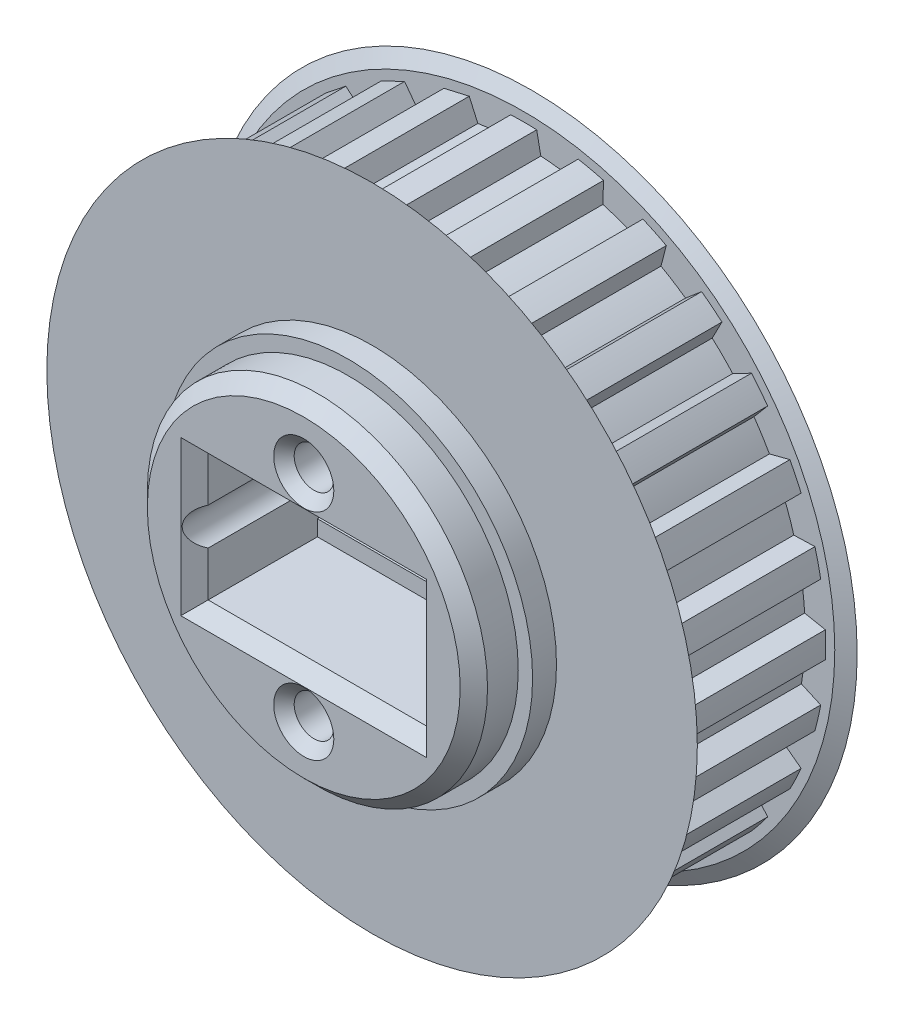
SolidWorks part; units mm, degrees
material "ABS"
ref_plane "Alzado" through (0, 0, 0) normal (0, 0, 1) x (1, 0, 0)
ref_plane "Planta" through (0, 0, 0) normal (0, 1, 0) x (1, 0, 0)
ref_plane "Vista lateral" through (0, 0, 0) normal (1, 0, 0) x (0, 0, -1)
sketch "Croquis1" plane through (0, 0, 0) normal (0, 0, 1) x (1, 0, 0)
  line L0 (0, 0) -> (0, 14.5885) construction
  line L1 (-0.95, 22.0796) -> (-1.25, 20.562)
  line L2 (0.95, 22.0796) -> (1.25, 20.562)
  line L3 (5.8393, 21.3146) -> (5.7941, 19.7684)
  line L4 (3.987, 21.7374) -> (3.3568, 20.3247)
  line L5 (10.4359, 19.4808) -> (10.0477, 17.9834)
  line L6 (8.724, 20.3052) -> (7.7953, 19.0681)
  line L7 (14.5091, 16.6702) -> (13.7975, 15.2967)
  line L8 (13.0236, 17.8548) -> (11.8429, 16.8554)
  line L9 (17.8548, 13.0236) -> (16.8554, 11.8429)
  line L10 (16.6702, 14.5091) -> (15.2967, 13.7975)
  line L11 (20.3052, 8.724) -> (19.0681, 7.7953)
  line L12 (19.4808, 10.4359) -> (17.9834, 10.0477)
  line L13 (21.7374, 3.987) -> (20.3247, 3.3568)
  line L14 (21.3146, 5.8393) -> (19.7684, 5.7941)
  line L15 (22.0796, -0.95) -> (20.562, -1.25)
  line L16 (22.0796, 0.95) -> (20.562, 1.25)
  line L17 (21.3146, -5.8393) -> (19.7684, -5.7941)
  line L18 (21.7374, -3.987) -> (20.3247, -3.3568)
  line L19 (19.4808, -10.4359) -> (17.9834, -10.0477)
  line L20 (20.3052, -8.724) -> (19.0681, -7.7953)
  line L21 (16.6702, -14.5091) -> (15.2967, -13.7975)
  line L22 (17.8548, -13.0236) -> (16.8554, -11.8429)
  line L23 (13.0236, -17.8548) -> (11.8429, -16.8554)
  line L24 (14.5091, -16.6702) -> (13.7975, -15.2967)
  line L25 (8.724, -20.3052) -> (7.7953, -19.0681)
  line L26 (10.4359, -19.4808) -> (10.0477, -17.9834)
  line L27 (3.987, -21.7374) -> (3.3568, -20.3247)
  line L28 (5.8393, -21.3146) -> (5.7941, -19.7684)
  line L29 (-0.95, -22.0796) -> (-1.25, -20.562)
  line L30 (0.95, -22.0796) -> (1.25, -20.562)
  line L31 (-5.8393, -21.3146) -> (-5.7941, -19.7684)
  line L32 (-3.987, -21.7374) -> (-3.3568, -20.3247)
  line L33 (-10.4359, -19.4808) -> (-10.0477, -17.9834)
  line L34 (-8.724, -20.3052) -> (-7.7953, -19.0681)
  line L35 (-14.5091, -16.6702) -> (-13.7975, -15.2967)
  line L36 (-13.0236, -17.8548) -> (-11.8429, -16.8554)
  line L37 (-17.8548, -13.0236) -> (-16.8554, -11.8429)
  line L38 (-16.6702, -14.5091) -> (-15.2967, -13.7975)
  line L39 (-20.3052, -8.724) -> (-19.0681, -7.7953)
  line L40 (-19.4808, -10.4359) -> (-17.9834, -10.0477)
  line L41 (-21.7374, -3.987) -> (-20.3247, -3.3568)
  line L42 (-21.3146, -5.8393) -> (-19.7684, -5.7941)
  line L43 (-22.0796, 0.95) -> (-20.562, 1.25)
  line L44 (-22.0796, -0.95) -> (-20.562, -1.25)
  line L45 (-21.3146, 5.8393) -> (-19.7684, 5.7941)
  line L46 (-21.7374, 3.987) -> (-20.3247, 3.3568)
  line L47 (-19.4808, 10.4359) -> (-17.9834, 10.0477)
  line L48 (-20.3052, 8.724) -> (-19.0681, 7.7953)
  line L49 (-16.6702, 14.5091) -> (-15.2967, 13.7975)
  line L50 (-17.8548, 13.0236) -> (-16.8554, 11.8429)
  line L51 (-13.0236, 17.8548) -> (-11.8429, 16.8554)
  line L52 (-14.5091, 16.6702) -> (-13.7975, 15.2967)
  line L53 (-14.5091, 16.6702) -> (-13.0236, 17.8548)
  line L54 (-8.724, 20.3052) -> (-7.7953, 19.0681)
  line L55 (-10.4359, 19.4808) -> (-10.0477, 17.9834)
  line L56 (-10.4359, 19.4808) -> (-8.724, 20.3052)
  line L57 (-3.987, 21.7374) -> (-3.3568, 20.3247)
  line L58 (-5.8393, 21.3146) -> (-5.7941, 19.7684)
  line L59 (-5.8393, 21.3146) -> (-3.987, 21.7374)
  arc A0 (-13.7975, 15.2967) -> (-15.2967, 13.7975) centre (0, 0) ccw
  arc A1 (3.3568, 20.3247) -> (1.25, 20.562) centre (0, 0) ccw
  arc A2 (-10.0477, 17.9834) -> (-11.8429, 16.8554) centre (0, 0) ccw
  arc A3 (-5.7941, 19.7684) -> (-7.7953, 19.0681) centre (0, 0) ccw
  arc A9 (-16.6702, 14.5091) -> (-17.8548, 13.0236) centre (0, 0) ccw
  arc A10 (-19.4808, 10.4359) -> (-20.3052, 8.724) centre (0, 0) ccw
  arc A11 (5.8393, 21.3146) -> (3.987, 21.7374) centre (0, 0) ccw
  arc A12 (0.95, 22.0796) -> (-0.95, 22.0796) centre (0, 0) ccw
  arc A16 (10.4359, 19.4808) -> (8.724, 20.3052) centre (0, 0) ccw
  arc A17 (14.5091, 16.6702) -> (13.0236, 17.8548) centre (0, 0) ccw
  arc A18 (17.8548, 13.0236) -> (16.6702, 14.5091) centre (0, 0) ccw
  arc A19 (20.3052, 8.724) -> (19.4808, 10.4359) centre (0, 0) ccw
  arc A20 (21.7374, 3.987) -> (21.3146, 5.8393) centre (0, 0) ccw
  arc A21 (22.0796, -0.95) -> (22.0796, 0.95) centre (0, 0) ccw
  arc A22 (21.3146, -5.8393) -> (21.7374, -3.987) centre (0, 0) ccw
  arc A23 (19.4808, -10.4359) -> (20.3052, -8.724) centre (0, 0) ccw
  arc A24 (16.6702, -14.5091) -> (17.8548, -13.0236) centre (0, 0) ccw
  arc A25 (13.0236, -17.8548) -> (14.5091, -16.6702) centre (0, 0) ccw
  arc A26 (-5.8393, -21.3146) -> (-3.987, -21.7374) centre (0, 0) ccw
  arc A27 (-10.4359, -19.4808) -> (-8.724, -20.3052) centre (0, 0) ccw
  arc A28 (-14.5091, -16.6702) -> (-13.0236, -17.8548) centre (0, 0) ccw
  arc A29 (-20.3052, -8.724) -> (-19.4808, -10.4359) centre (0, 0) ccw
  arc A30 (-21.7374, -3.987) -> (-21.3146, -5.8393) centre (0, 0) ccw
  arc A31 (-22.0796, 0.95) -> (-22.0796, -0.95) centre (0, 0) ccw
  arc A32 (-21.3146, 5.8393) -> (-21.7374, 3.987) centre (0, 0) ccw
  arc A33 (-0.95, -22.0796) -> (0.95, -22.0796) centre (0, 0) ccw
  arc A34 (3.987, -21.7374) -> (5.8393, -21.3146) centre (0, 0) ccw
  arc A35 (8.724, -20.3052) -> (10.4359, -19.4808) centre (0, 0) ccw
  arc A36 (7.7953, 19.0681) -> (5.7941, 19.7684) centre (0, 0) ccw
  arc A37 (11.8429, 16.8554) -> (10.0477, 17.9834) centre (0, 0) ccw
  arc A39 (-1.25, 20.562) -> (-3.3568, 20.3247) centre (0, 0) ccw
  arc A43 (15.2967, 13.7975) -> (13.7975, 15.2967) centre (0, 0) ccw
  arc A44 (17.9834, 10.0477) -> (16.8554, 11.8429) centre (0, 0) ccw
  arc A45 (19.7684, 5.7941) -> (19.0681, 7.7953) centre (0, 0) ccw
  arc A46 (20.562, 1.25) -> (20.3247, 3.3568) centre (0, 0) ccw
  arc A47 (20.3247, -3.3568) -> (20.562, -1.25) centre (0, 0) ccw
  arc A48 (19.0681, -7.7953) -> (19.7684, -5.7941) centre (0, 0) ccw
  arc A49 (16.8554, -11.8429) -> (17.9834, -10.0477) centre (0, 0) ccw
  arc A50 (13.7975, -15.2967) -> (15.2967, -13.7975) centre (0, 0) ccw
  arc A51 (10.0477, -17.9834) -> (11.8429, -16.8554) centre (0, 0) ccw
  arc A52 (5.7941, -19.7684) -> (7.7953, -19.0681) centre (0, 0) ccw
  arc A53 (1.25, -20.562) -> (3.3568, -20.3247) centre (0, 0) ccw
  arc A54 (-3.3568, -20.3247) -> (-1.25, -20.562) centre (0, 0) ccw
  arc A55 (-7.7953, -19.0681) -> (-5.7941, -19.7684) centre (0, 0) ccw
  arc A56 (-11.8429, -16.8554) -> (-10.0477, -17.9834) centre (0, 0) ccw
  arc A57 (-15.2967, -13.7975) -> (-13.7975, -15.2967) centre (0, 0) ccw
  arc A58 (-17.9834, -10.0477) -> (-16.8554, -11.8429) centre (0, 0) ccw
  arc A59 (-19.7684, -5.7941) -> (-19.0681, -7.7953) centre (0, 0) ccw
  arc A60 (-20.562, -1.25) -> (-20.3247, -3.3568) centre (0, 0) ccw
  arc A61 (-20.3247, 3.3568) -> (-20.562, 1.25) centre (0, 0) ccw
  arc A62 (-19.0681, 7.7953) -> (-19.7684, 5.7941) centre (0, 0) ccw
  arc A63 (-16.8554, 11.8429) -> (-17.9834, 10.0477) centre (0, 0) ccw
  arc A71 (-17.8548, -13.0236) -> (-16.6702, -14.5091) centre (0, 0) ccw
  circle A72 centre (0, 0) radius 1.5
  point P151 (0, 0)
  dimension "D1" = 22.1
  dimension "D6" = 3
  dimension "D5" = 1.5
  dimension "D2" = 2.5
  dimension "D3" = 1.9
  dimension "D4" = 28
extrude "Saliente-Extruir1" add sketch "Croquis1" along normal blind 10.5
sketch "Croquis2" plane through (0, 0, 10.5) normal (0, 0, 1) x (1, 0, 0)
  circle A0 centre (0, 0) radius 24.5
  circle A1 centre (0, 0) radius 1.5
  circle A2 centre (0, 0) radius 1.5 construction
  dimension "D1" = 49
extrude "Saliente-Extruir2" add sketch "Croquis2" along normal blind 0.6
sketch "Croquis3" plane through (0, 0, 11.1) normal (0, 0, 1) x (1, 0, 0)
  circle A0 centre (0, 0) radius 1.5
  circle A1 centre (0, 0) radius 12.45
  circle A3 centre (0, 0) radius 1.5 construction
  dimension "D1" = 24.9
sketch "Croquis4" plane through (0, 0, 0) normal (0, 0, -1) x (-1, 0, 0)
  circle A0 centre (0, 0) radius 1.5
  circle A1 centre (0, 0) radius 12.45
  circle A2 centre (0, 0) radius 1.5 construction
  dimension "D1" = 24.9
extrude "Saliente-Extruir4" add sketch "Croquis4" along normal blind 5
sketch "Croquis6" plane through (0, 0, 0) normal (0, 0, -1) x (-1, 0, 0)
  circle A0 centre (0, 0) radius 24.5
  circle A1 centre (0, 0) radius 1.5
  circle A2 centre (0, 0) radius 1.5 construction
  dimension "D1" = 49
extrude "Saliente-Extruir6" add sketch "Croquis6" along normal blind 0.6
sketch "Croquis5" plane through (0, 0, -0.6) normal (0, 0, -1) x (-1, 0, 0)
  circle A0 centre (0, 0) radius 1.5
  circle A1 centre (0, 0) radius 13.5
  circle A2 centre (0, 0) radius 1.5 construction
  dimension "D1" = 27
extrude "Saliente-Extruir5" add sketch "Croquis5" along normal blind 1.9
chamfer "Chaflán2" distance 1 angle 60 2 edges at (-24.5, 0, 0) (24.5, 0, 10.5)
extrude "Saliente-Extruir7" add sketch "Croquis3" along normal blind 5
chamfer "Chaflán4" distance 1 angle 45 1 edges at (12.45, 0, 16.1)
sketch "Croquis7" plane through (0, 0, 11.1) normal (0, 0, 1) x (1, 0, 0)
  circle A0 centre (0, 0) radius 1.5
  circle A1 centre (0, 0) radius 13.5
  circle A2 centre (0, 0) radius 1.5 construction
  dimension "D1" = 27
extrude "Saliente-Extruir8" add sketch "Croquis7" along normal blind 1.75
sketch "Croquis8" plane through (0, 0, 0) normal (0, 0, 1) x (1, 0, 0)
  line L0 (0, 0) -> (6.706, 0) construction
  line L1 (-8, 3.5) -> (8, 3.5)
  line L2 (-8, 3.5) -> (-8, -3.5)
  line L3 (-8, -3.5) -> (8, -3.5)
  line L4 (8, 3.5) -> (8, -3.5)
  line L5 (-8, 3.5) -> (8, -3.5) construction
  line L6 (-8, -3.5) -> (8, 3.5) construction
  circle A0 centre (0, 7.8756) radius 1.45
  circle A1 centre (0, -7.8756) radius 1.45
  point P0 (0, 0)
  dimension "D1" = 2.9
  dimension "D2" = 7
  dimension "D3" = 16
extrude "Cortar-Extruir1" cut sketch "Croquis8" against normal through all both and the other way through all
sketch "Croquis10" plane through (0, 0, 16.1) normal (0, 0, 1) x (1, 0, 0)
  line L1 (8, 4.65) -> (-8, 4.65)
  line L2 (8, 4.65) -> (8, -4.65)
  line L3 (8, -4.65) -> (-8, -4.65)
  line L4 (-8, 4.65) -> (-8, -4.65)
  line L5 (8, 4.65) -> (-8, -4.65) construction
  line L6 (8, -4.65) -> (-8, 4.65) construction
  point P0 (0, 0)
  dimension "D1" = 9.3
  dimension "D2" = 16
extrude "Cortar-Extruir3" cut sketch "Croquis10" against normal blind 9
chamfer "Chaflán5" distance 1 angle 45 8 edges at (-8, 0, -5) (0, 3.5, -5) (8, 0, -5) (0, -3.5, -5) (8, 0, 16.1) (-8, 0, 16.1) (0, 4.65, 16.1) (0, -4.65, 16.1)
sketch "Sketch1" plane through (0, 0, -5) normal (0, 0, -1) x (-1, 0, 0)
  circle A0 centre (0, 0) radius 12.45
  circle A1 centre (0, 0) radius 12.45 construction
  circle A2 centre (0, 7.8756) radius 1.45
  circle A3 centre (0, -7.8756) radius 1.45
  circle A4 centre (0, 7.8756) radius 1.45 construction
extrude "Boss-Extrude1" add sketch "Sketch1" against normal blind 5
sketch "Sketch2" plane through (0, 0, -5) normal (0, 0, -1) x (-1, 0, 0)
  line L0 (0, 17.274) -> (0, -20.0751) construction
  line L1 (-7.5, 0) -> (7.5, 0) construction
  circle A0 centre (-7.5, 0) radius 1.45
  circle A1 centre (7.5, 0) radius 1.45
  dimension "D1" = 2.9
  dimension "D2" = 15
extrude "Cut-Extrude1" cut sketch "Sketch2" against normal through all
sketch "Sketch4" plane through (0, 0, 16.1) normal (0, 0, 1) x (1, 0, 0)
  line L0 (-8, -3.5) -> (8, -3.5) construction
  line L1 (4, 3.5) -> (-4, 3.5)
  line L2 (4, 3.5) -> (4, -3.5)
  line L3 (4, -3.5) -> (-4, -3.5)
  line L4 (-4, 3.5) -> (-4, -3.5)
  line L5 (4, 3.5) -> (-4, -3.5) construction
  line L6 (4, -3.5) -> (-4, 3.5) construction
  point P0 (0, 0)
  dimension "D1" = 8
extrude "Cut-Extrude2" cut sketch "Sketch4" against normal blind 30
chamfer "Chamfer3" distance 1 angle 45 4 edges at (-4, 0, -5) (0, 3.5, -5) (4, 0, -5) (0, -3.5, -5)
chamfer "Chamfer2" distance 0.75 angle 45 1 edges at (-12.45, 0, -5)
chamfer "Chamfer4" distance 0.75 angle 45 4 edges at (1.45, -7.8756, 16.1) (1.45, 7.8756, 16.1) (6.05, 0, -5) (-6.05, 0, -5)
